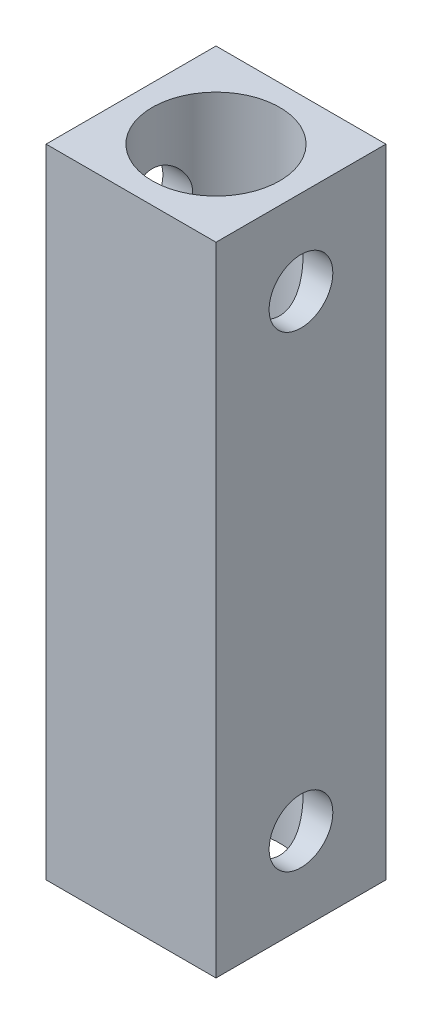
SolidWorks part; units mm, degrees
ref_plane "Front Plane" through (0, 0, 0) normal (0, 0, 1) x (1, 0, 0)
ref_plane "Top Plane" through (0, 0, 0) normal (0, 1, 0) x (1, 0, 0)
ref_plane "Right Plane" through (0, 0, 0) normal (1, 0, 0) x (0, 0, -1)
sketch "Sketch1" plane through (0, 0, 0) normal (0, 1, 0) x (1, 0, 0)
  line L1 (-4, -4) -> (4, -4)
  line L2 (-4, -4) -> (-4, 4)
  line L3 (-4, 4) -> (4, 4)
  line L4 (4, -4) -> (4, 4)
  line L5 (-4, -4) -> (4, 4) construction
  line L6 (-4, 4) -> (4, -4) construction
  circle A0 centre (0, 0) radius 3
  point P0 (0, 0)
  dimension "D1" = 6
  dimension "D2" = 4
extrude "Boss-Extrude2" add sketch "Sketch1" along normal blind 30
sketch "Sketch2" plane through (4, 0, 0) normal (1, 0, 0) x (0, 0, -1)
  line L0 (-4, 0) -> (4, 0) construction
  line L2 (-4, 30) -> (4, 30) construction
  line L3 (4, 15) -> (-4, 15) construction
  line L4 (4, 30) -> (4, 0) construction
  line L5 (-4, 30) -> (-4, 0) construction
  circle A0 centre (0, 26) radius 1.5
  circle A1 centre (0, 4) radius 1.5
  point P6 (0, 0)
  dimension "D1" = 3
  dimension "D2" = 4
extrude "Cut-Extrude1" cut sketch "Sketch2" against normal up to surface (8 mm away) up to face at (-4, 15, 0)
